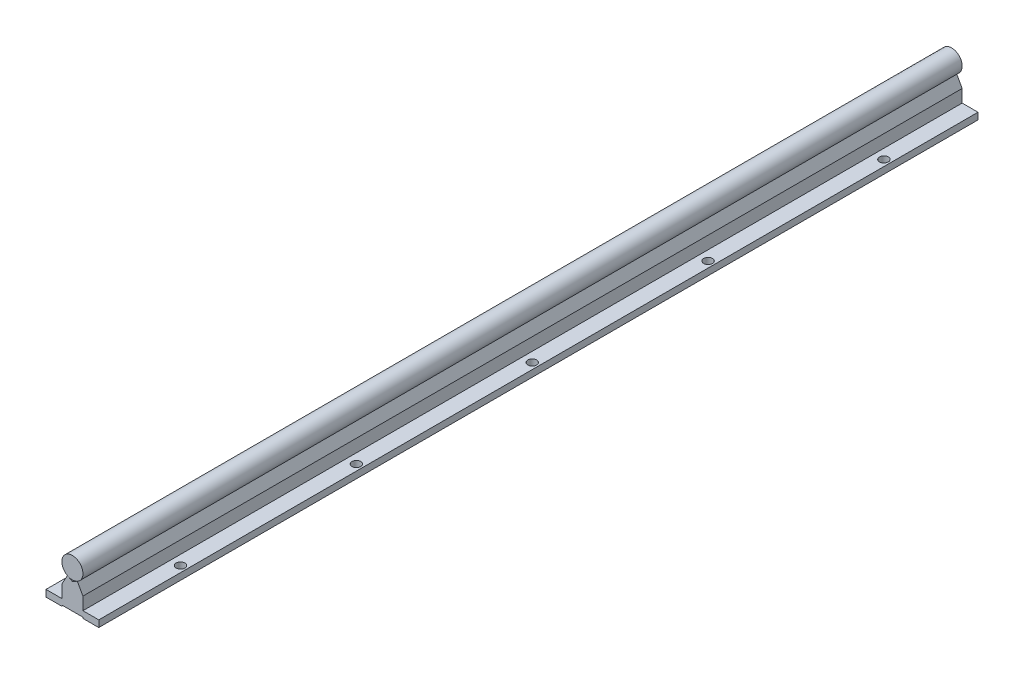
SolidWorks part; units mm, degrees
ref_plane "Alzado" through (0, 0, 0) normal (0, 0, 1) x (1, 0, 0)
ref_plane "Planta" through (0, 0, 0) normal (0, 1, 0) x (1, 0, 0)
ref_plane "Vista lateral" through (0, 0, 0) normal (1, 0, 0) x (0, 0, -1)
sketch "Croquis1" plane through (0, 0, 0) normal (0, 0, 1) x (1, 0, 0)
  line L0 (0, 0) -> (0, -22) construction
  line L1 (0, -22) -> (15, -22) construction
  line L2 (3.5, 0) -> (3.5, -22) construction
  line L3 (6, -22) -> (6, 5.4102) construction
  line L4 (-13.9204, -11) -> (10.0172, -11) construction
  line L5 (0, -6.8) -> (2.8235, -5.2941)
  line L6 (2.8235, -5.2941) -> (6, -11)
  line L7 (6, -11) -> (6, -18.2)
  line L8 (6, -18.2) -> (15, -18.2)
  line L9 (15, -18.2) -> (15, -22)
  line L10 (-6, -21.4) -> (6, -21.4)
  line L11 (6, -21.4) -> (6, -22)
  line L12 (6, -22) -> (15, -22)
  line L13 (-6, -21.4) -> (-6, -22)
  line L14 (-6, -22) -> (-15, -22)
  line L15 (-15, -18.2) -> (-15, -22)
  line L16 (-6, -18.2) -> (-15, -18.2)
  line L17 (-6, -11) -> (-6, -18.2)
  line L18 (-2.8235, -5.2941) -> (-6, -11)
  line L19 (0, -6.8) -> (-2.8235, -5.2941)
  circle A0 centre (0, 0) radius 6
  point P17 (0, -6)
  point P21 (0, -21.4)
  dimension "D1" = 12
  dimension "D2" = 22
  dimension "D3" = 15
  dimension "D4" = 3.5
  dimension "D5" = 6
  dimension "D6" = 11
  dimension "D7" = 0.8
  dimension "D8" = 3.8
  dimension "D9" = 0.6
extrude "Saliente-Extruir1" add sketch "Croquis1" along normal blind 500 contours L5 L19 L18 L17 L16 L15 L14 L13 L10 L11 L12 L9 L8 L7 L6 | A0 region at (0, -15.8774, 0) region at (0, 0, 0)
sketch "Croquis2" plane through (0, -18.2, 0) normal (0, 1, 0) x (1, 0, 0)
  line L0 (-11.5, 0) -> (-11.5, -500) construction
  line L1 (-6, 0) -> (-15, 0) construction
  line L2 (-6, -500) -> (-15, -500) construction
  line L3 (-15, -500) -> (-15, 0) construction
  circle A0 centre (-11.5, -50) radius 2.5
  circle A1 centre (-11.5, -150) radius 2.5
  circle A2 centre (-11.5, -250) radius 2.5
  circle A3 centre (-11.5, -350) radius 2.5
  circle A4 centre (-11.5, -450) radius 2.5
  dimension "D2" = 5
  dimension "D1" = 3.5
  dimension "D3" = 50
  dimension "D4" = 5
extrude "Cortar-Extruir1" cut sketch "Croquis2" against normal up to surface (3.8 mm away) up to face at (-10.5, -22, 250)
mirror "Simetría1" about plane through (0, 0, 0) normal (1, 0, 0) of "Cortar-Extruir1"
ref_plane "Plano1" through (0, 0, 250) normal (0, 0, -1) x (-1, 0, 0)
equation "\"D4@Croquis1\"=7/2"
